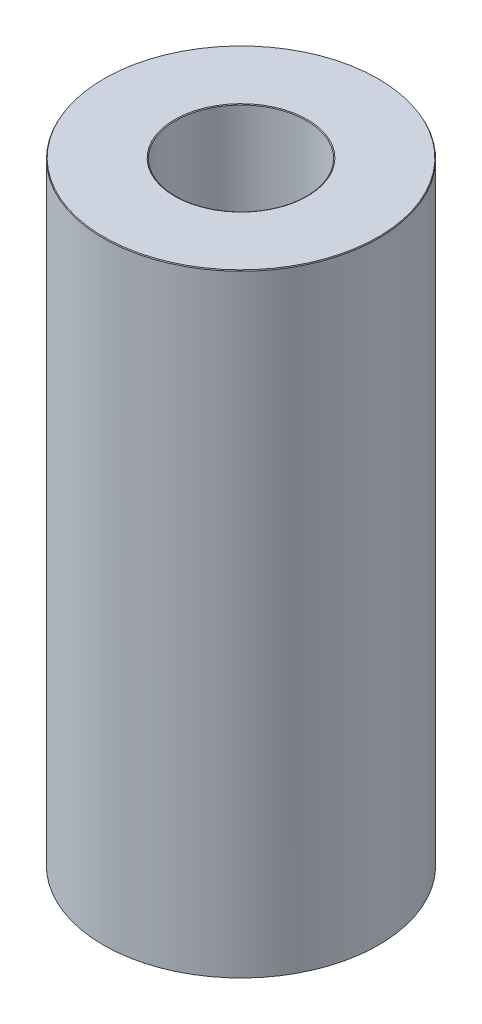
SolidWorks part; units mm, degrees
ref_plane "Front Plane" through (0, 0, 0) normal (0, 0, 1) x (1, 0, 0)
ref_plane "Top Plane" through (0, 0, 0) normal (0, 1, 0) x (1, 0, 0)
ref_plane "Right Plane" through (0, 0, 0) normal (1, 0, 0) x (0, 0, -1)
sketch "Sketch1" plane through (0, 0, 0) normal (0, 1, 0) x (1, 0, 0)
  circle A0 centre (0, 0) radius 37.5
  dimension "SLEEVE_OD" = 75
extrude "Boss-Extrude1" add sketch "Sketch1" along normal blind 167.1692
sketch "Sketch2" plane through (0, 0, 0) normal (0, 1, 0) x (1, 0, 0)
  circle A0 centre (0, 0) radius 17.8608
  dimension "BORE_D" = 35.7215
extrude "Cut-Extrude1" cut sketch "Sketch2" along normal through all
chamfer "Chamfer1" distance 0.237 angle 30 4 edges at (0, 167.1692, 17.8608) (0, 0, 17.8608) (0, 0, 37.5) (0, 167.1692, 37.5) first distance on face at (0, 167.1692, 17.8608) first distance on face at (0, 0, 17.8608) first distance on face at (0, 167.1692, 37.5)
